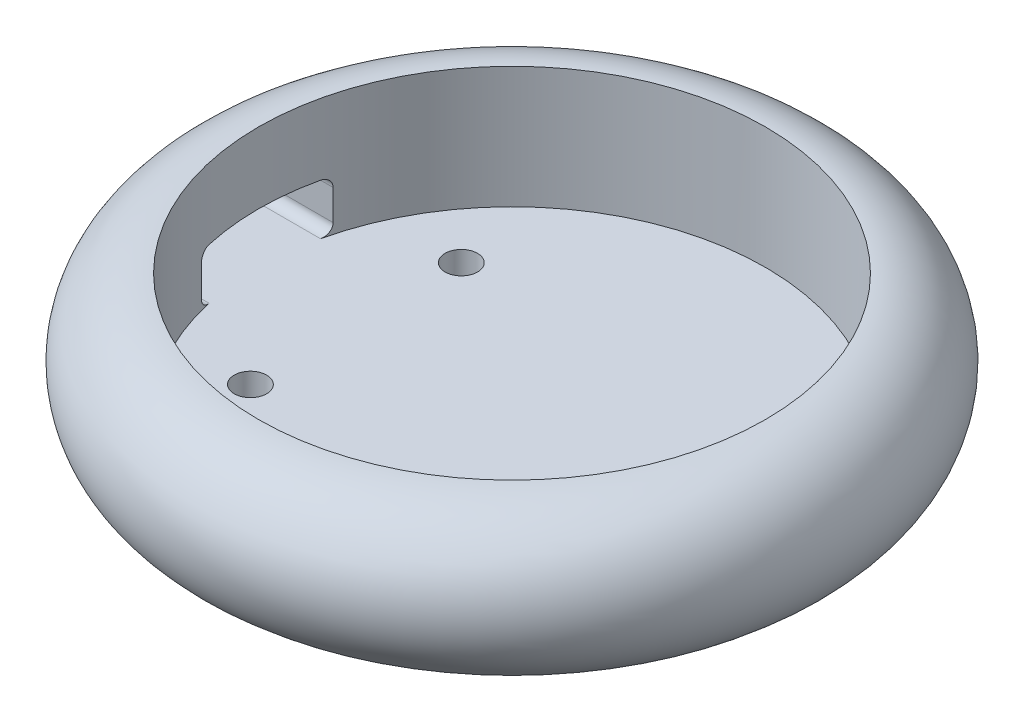
SolidWorks part; units mm, degrees
ref_plane "Front Plane" through (0, 0, 0) normal (0, 0, 1) x (1, 0, 0)
ref_plane "Top Plane" through (0, 0, 0) normal (0, 1, 0) x (1, 0, 0)
ref_plane "Right Plane" through (0, 0, 0) normal (1, 0, 0) x (0, 0, -1)
sketch "Sketch1" plane through (0, 0, 0) normal (0, 0, 1) x (1, 0, 0)
  line L0 (0, -4.3713) -> (0, 10.6287)
  line L1 (0, -4.3713) -> (-25, -4.3713)
  line L3 (0, 10.6287) -> (-25, 10.6287)
  line L5 (0, 0) -> (-26.494, 1.4003) construction
  line L6 (0, 0) -> (-27.6779, -7.5937) construction
  line L7 (-25, -4.3713) -> (-25, 10.6287) construction
  arc A2 (-25, 10.6287) -> (-25, -4.3713) centre (-25, 3.1287) ccw
  point P0 (0, 0)
  dimension "D1" = 25
  dimension "D2" = 15
revolve "Revolve1" add sketch "Sketch1" angle 360 about L0
ref_plane "Plane1" through (0, 10.6287, 0) normal (0, 1, 0) x (1, 0, 0)
sketch "Sketch3" plane through (0, 10.6287, 0) normal (0, 1, 0) x (1, 0, 0)
  circle A0 centre (0, 0) radius 25
extrude "Cut-Extrude2" cut sketch "Sketch3" against normal blind 12
ref_plane "Plane2" through (0, -1.3713, 0) normal (0, 1, 0) x (1, 0, 0)
sketch "Sketch4" plane through (0, -1.3713, 0) normal (0, 1, 0) x (1, 0, 0)
  line L0 (0, 0) -> (0, 6.4336) construction
  line L5 (15.4, -10.4) -> (-15.4, 10.4) construction
  line L6 (15.4, 10.4) -> (-15.4, -10.4) construction
  line L7 (0, 0) -> (-6.1164, 0) construction
  circle A0 centre (-15.4, 10.4) radius 1.6
  circle A1 centre (15.4, 10.4) radius 1.6
  circle A2 centre (15.4, -10.4) radius 1.6
  circle A3 centre (-15.4, -10.4) radius 1.6
  point P0 (0, 0)
  dimension "D3" = 3.2
  dimension "D1" = 30.8
  dimension "D2" = 20.8
extrude "Cut-Extrude3" cut sketch "Sketch4" against normal blind 6
sketch "Sketch5" plane through (0, -4.3713, 0) normal (0, -1, 0) x (1, 0, 0)
  circle A0 centre (0, 0) radius 1.5
  dimension "D1" = 3
extrude "Cut-Extrude4" cut sketch "Sketch5" against normal blind 1
sketch "Sketch8" plane through (0, 0, 0) normal (1, 0, 0) x (0, 0, -1)
  line L0 (0, -4.3713) -> (0, -1.3713) construction
  line L1 (-25, -4.3713) -> (25, -4.3713) construction
  line L2 (0, -1.3713) -> (0, 1.1287) construction
  line L4 (-5.5, 3.6287) -> (5.5, 3.6287)
  line L5 (-6.5, 2.6287) -> (-6.5, -0.3713)
  line L6 (-5.5, -1.3713) -> (5.5, -1.3713)
  line L7 (6.5, 2.6287) -> (6.5, -0.3713)
  line L8 (-6.5, 3.6287) -> (6.5, -1.3713) construction
  line L9 (-6.5, -1.3713) -> (6.5, 3.6287) construction
  arc A0 (6.5, -0.3713) -> (5.5, -1.3713) centre (5.5, -0.3713) cw
  arc A1 (6.5, 2.6287) -> (5.5, 3.6287) centre (5.5, 2.6287) ccw
  arc A2 (-5.5, -1.3713) -> (-6.5, -0.3713) centre (-5.5, -0.3713) cw
  arc A3 (-6.5, 2.6287) -> (-5.5, 3.6287) centre (-5.5, 2.6287) cw
  dimension "D4" = 1
  dimension "D1" = 3
  dimension "D2" = 2.5
  dimension "D3" = 13
extrude "Cut-Extrude6" cut sketch "Sketch8" against normal through all
